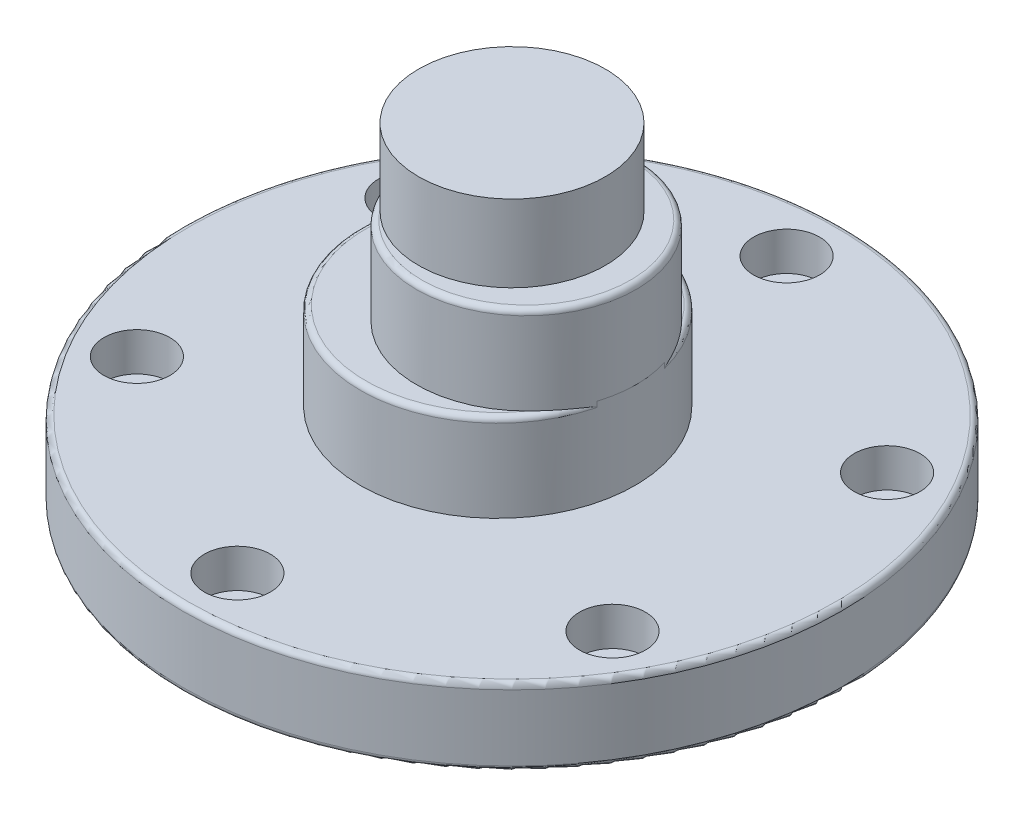
SolidWorks part; units mm, degrees
ref_plane "Front Plane" through (0, 0, 0) normal (0, 0, 1) x (1, 0, 0)
ref_plane "Top Plane" through (0, 0, 0) normal (0, 1, 0) x (1, 0, 0)
ref_plane "Right Plane" through (0, 0, 0) normal (1, 0, 0) x (0, 0, -1)
sketch "Sketch1" plane through (0, 0, 0) normal (0, 1, 0) x (1, 0, 0)
  circle A0 centre (0, 0) radius 25 construction
  circle A1 centre (0, 0) radius 30
  circle A2 centre (0, 25) radius 1.65
  circle A3 centre (21.6506, 12.5) radius 1.65
  circle A4 centre (21.6506, -12.5) radius 1.65
  circle A5 centre (0, -25) radius 1.65
  circle A6 centre (-21.6506, -12.5) radius 1.65
  circle A7 centre (-21.6506, 12.5) radius 1.65
  point P18 (0, 0)
  dimension "D1" = 50
  dimension "D2" = 60
  dimension "D3" = 3.3
  dimension "D4" = 6
extrude "Boss-Extrude1" add sketch "Sketch1" along normal blind 7
sketch "Sketch2" plane through (0, 7, 0) normal (0, 1, 0) x (1, 0, 0)
  circle A0 centre (-1.3, 0) radius 12.5
  point P0 (0, 0)
  point P1 (-1.3, 0)
  dimension "D2" = 25
  dimension "D1" = 1.3
extrude "Boss-Extrude2" add sketch "Sketch2" along normal blind 8
sketch "Sketch3" plane through (0, 15, 0) normal (0, 1, 0) x (1, 0, 0)
  circle A0 centre (1.3, 0) radius 10
  point P0 (1.3, 0)
  dimension "D2" = 20
  dimension "D1" = 1.3
extrude "Boss-Extrude3" add sketch "Sketch3" along normal blind 8
fillet "Fillet1" radius 0.5 4 edges at (1.3, 23, 10) (-13.8, 15, 0) (0, 0, 30) (0, 7, 30)
sketch "Sketch4" plane through (0, 7, 0) normal (0, 1, 0) x (1, 0, 0)
  circle A0 centre (0, 25) radius 3
  circle A1 centre (21.6506, 12.5) radius 3
  circle A2 centre (21.6506, -12.5) radius 3
  circle A3 centre (0, -25) radius 3
  circle A4 centre (-21.6506, -12.5) radius 3
  circle A5 centre (-21.6506, 12.5) radius 3
  point P16 (0, 0)
  dimension "D1" = 6
  dimension "D2" = 6
extrude "Cut-Extrude1" cut sketch "Sketch4" against normal blind 3.5
sketch "Sketch5" plane through (0, 23, 0) normal (0, 1, 0) x (1, 0, 0)
  circle A0 centre (0, 0) radius 8.5
  dimension "D1" = 17
extrude "Boss-Extrude4" add sketch "Sketch5" along normal blind 7
